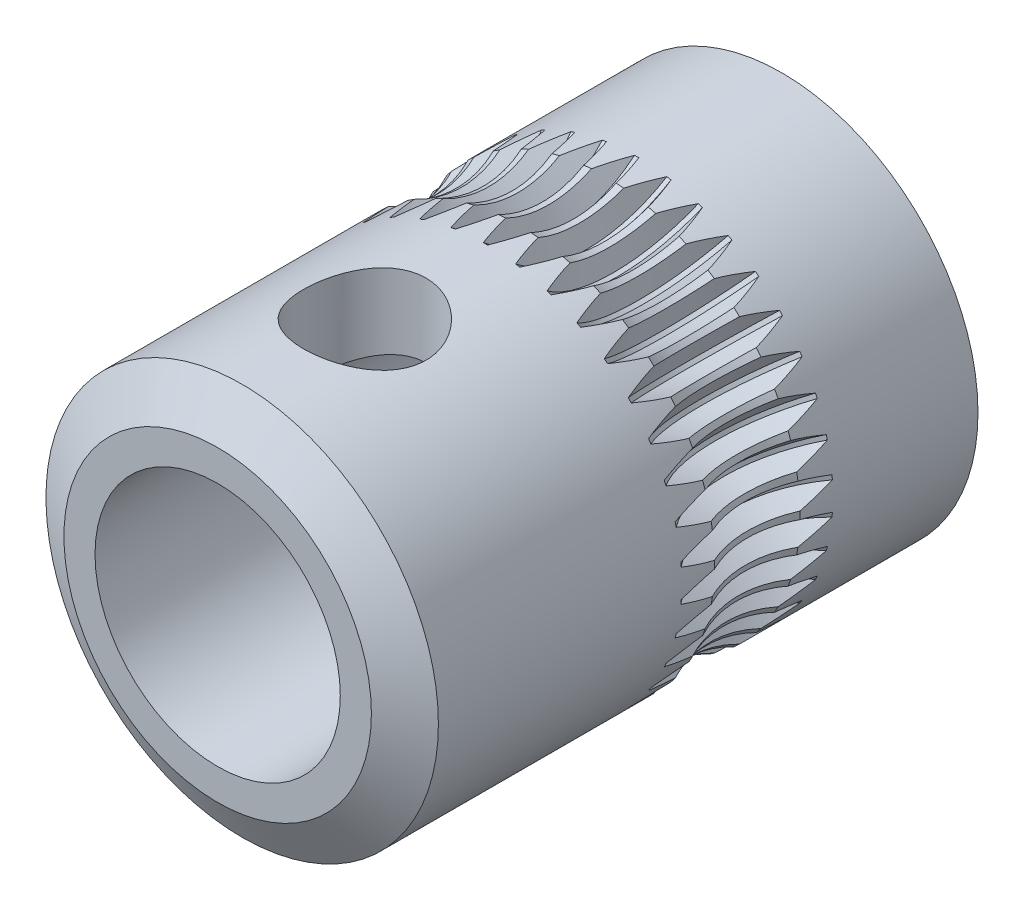
SolidWorks part; units mm, degrees
ref_plane "Front Plane" through (0, 0, 0) normal (0, 0, 1) x (1, 0, 0)
ref_plane "Top Plane" through (0, 0, 0) normal (0, 1, 0) x (1, 0, 0)
ref_plane "Right Plane" through (0, 0, 0) normal (1, 0, 0) x (0, 0, -1)
sketch "Sketch1" plane through (0, 0, 0) normal (0, 0, 1) x (1, 0, 0)
  circle A0 centre (0, 0) radius 4
  circle A1 centre (0, 0) radius 2.5
  dimension "D1" = 8
  dimension "D2" = 5
extrude "Boss-Extrude1" add sketch "Sketch1" along normal blind 12
chamfer "Chamfer1" distance 0.5 angle 60 1 edges at (4, 0, 12) first distance on face at (4, 0, 12)
ref_plane "Plane1" through (0, 0, 5) normal (0, 0, -1) x (-1, 0, 0)
sketch "Sketch2" plane through (0, 0, 0) normal (1, 0, 0) x (0, 0, -1)
  line L0 (-5, -4.4) -> (-5, 4.4) construction
  line L1 (0, 0) -> (-12.0979, 0) construction
  circle A0 centre (-5, 5.8) radius 2
  dimension "D1" = 4
  dimension "D2" = 5.8
revolve "Cut-Revolve1" cut sketch "Sketch2" angle 360 about L1
sketch "Sketch3" plane through (3.2, 0, 5) normal (0, 0, 1) x (1, 0, 0)
  line L0 (-3.2, 3.43) -> (-3.2, 3.8) construction
  line L1 (-3.4574, 3.8) -> (-2.9426, 3.8) construction
  line L2 (-5.0425, 5.8) -> (-2.1511, 5.8) construction
  line L3 (-3.2437, 3.43) -> (-3.1562, 3.43)
  line L4 (-3.1562, 3.43) -> (-2.9426, 3.8)
  line L5 (-2.9426, 3.8) -> (-2.1511, 3.8)
  line L6 (-2.1511, 3.8) -> (-2.1511, 4.3976)
  line L7 (-2.1511, 4.3976) -> (-4.2489, 4.3976)
  line L8 (-4.2489, 4.3976) -> (-4.2489, 3.8)
  line L9 (-4.2489, 3.8) -> (-3.4574, 3.8)
  line L10 (-3.4574, 3.8) -> (-3.2437, 3.43)
  point P15 (-3.2, 0)
  dimension "D1" = 2
  dimension "D2" = 5.8
  dimension "D3" = 0.0875
  dimension "D4" = 0.37
  dimension "D5" = 60
revolve "Cut-Revolve2" cut sketch "Sketch3" angle 360 about L2
ref_axis "Axis1" through (0, 0, 12) along (0, 0, -1)
pattern_circular "CirPattern1" count 38 over 360 about axis through (0, 0, 12) along (0, 0, -1) of "Cut-Revolve2"
chamfer "Chamfer2" distance 0.5 angle 60 1 edges at (4, 0, 0) first distance on face at (0, 0, 3.7934)
hole_wizard "M3 Tapped Hole1" positions "Sketch5" profile "Sketch4" tap size "M3" standard "ISO" end condition through all
sketch "Sketch5" plane through (0, 0, 0) normal (0, 1, 0) x (1, 0, 0)
  line L0 (0, -12) -> (0, 0) construction
  line L1 (-3.134, -12) -> (3.134, -12) construction
  point P0 (0, -9)
  dimension "D1" = 3
sketch "Sketch4" plane through (0, 0, 9) normal (1, 0, 0) x (0, 0, -1)
  line L0 (0, 0) -> (0, 4.1047)
  line L1 (0, 4.1047) -> (1.25, 4.1047)
  line L2 (1.25, 4.1047) -> (1.25, 0)
  line L5 (1.25, 0) -> (0, 0)
  line L11 (0, -6.35) -> (0, 107.95) construction
  dimension "Thru Tap Drill Dia." = 2.5
  dimension "Thru Tap Drill Depth" = 4.1047
cosmetic thread "Hole Thread1" parameters "D2"=3
equation "\"D2@Sketch2\"=(7.6+4)/2"
